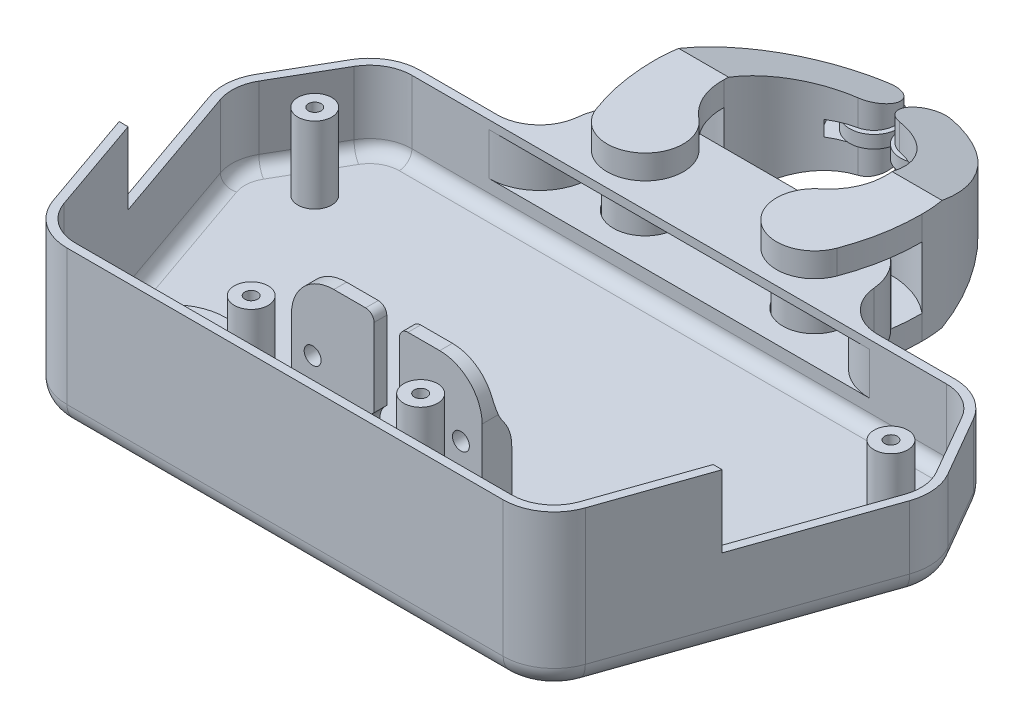
SolidWorks part; units mm, degrees
ref_plane "Front Plane" through (0, 0, 0) normal (0, 0, 1) x (1, 0, 0)
ref_plane "Top Plane" through (0, 0, 0) normal (0, 1, 0) x (1, 0, 0)
ref_plane "Right Plane" through (0, 0, 0) normal (1, 0, 0) x (0, 0, -1)
sketch "Sketch1" plane through (0, 0, 0) normal (0, 1, 0) x (1, 0, 0)
  line L0 (-70, -55) -> (-35, -55)
  line L1 (70, -55) -> (84.4338, -80)
  line L2 (84.4338, -80) -> (60, -150)
  line L3 (60, -150) -> (-60, -150)
  line L4 (-60, -150) -> (-84.4338, -80)
  line L5 (-84.4338, -80) -> (-70, -55)
  line L6 (-35, -55) -> (-35, -35)
  line L7 (-35, -35) -> (35, -35)
  line L8 (35, -35) -> (35, -55)
  line L9 (0, -55) -> (0, -122.8119) construction
  line L10 (35, -55) -> (70, -55)
  point P15 (0, -150)
  dimension "D1" = 25
  dimension "D2" = 140
  dimension "D3" = 70
  dimension "D4" = 120
  dimension "D5" = 70
  dimension "D6" = 55
  dimension "D7" = 120
  dimension "D8" = 20
  dimension "D9" = 70
  dimension "D10" = 35
extrude "Boss-Extrude1" add sketch "Sketch1" along normal blind 2
sketch "Sketch2" plane through (0, 2, 0) normal (0, 1, 0) x (1, 0, 0)
  line L0 (84.4338, -80) -> (70, -55) construction
  line L1 (60, -150) -> (84.4338, -80) construction
  line L2 (-60, -150) -> (60, -150) construction
  line L3 (-84.4338, -80) -> (-60, -150) construction
  line L4 (-70, -55) -> (-84.4338, -80) construction
  line L6 (84.4338, -80) -> (70, -55)
  line L7 (60, -150) -> (84.4338, -80)
  line L8 (-60, -150) -> (60, -150)
  line L9 (-84.4338, -80) -> (-60, -150)
  line L10 (-70, -55) -> (-84.4338, -80)
  line L11 (70, -55) -> (35, -55)
  line L12 (68.8453, -57) -> (33, -57)
  line L13 (-68.8453, -57) -> (-82.2434, -80.2062)
  line L14 (-82.2434, -80.2062) -> (-58.5798, -148)
  line L15 (-58.5798, -148) -> (58.5798, -148)
  line L16 (58.5798, -148) -> (82.2434, -80.2062)
  line L17 (82.2434, -80.2062) -> (68.8453, -57)
  line L18 (-35, -55) -> (-35, -35)
  line L19 (-35, -35) -> (35, -35)
  line L20 (35, -35) -> (35, -55)
  line L21 (-35, -55) -> (-70, -55)
  line L22 (-33, -57) -> (-33, -37)
  line L23 (70, -55) -> (-70, -55) construction
  line L24 (-33, -37) -> (33, -37)
  line L25 (33, -37) -> (33, -57)
  line L26 (-33, -57) -> (-68.8453, -57)
  line L28 (68.8453, -57) -> (-68.8453, -57) construction
  dimension "D1" = 2
  dimension "D2" = 2
  dimension "D3" = 2
  dimension "D4" = 2
extrude "Boss-Extrude2" add sketch "Sketch2" along normal blind 35
sketch "Sketch20" plane through (0, 0, 0) normal (0, -1, 0) x (1, 0, 0)
  line L0 (70, 55) -> (35, 55) construction
  line L1 (-35, 35) -> (35, 35)
  line L2 (-35, 35) -> (-35, 55)
  line L3 (-35, 55) -> (35, 55)
  line L4 (35, 35) -> (35, 55)
  line L5 (35, 55) -> (35, 35) construction
  line L6 (35, 35) -> (-35, 35) construction
  line L7 (-35, 35) -> (-35, 55) construction
extrude "Cut-Extrude7" cut sketch "Sketch20" against normal blind 8
sketch "Sketch21" plane through (0, 8, 0) normal (0, -1, 0) x (1, 0, 0)
  line L1 (-35, 35) -> (35, 35)
  line L2 (-35, 35) -> (-35, 55)
  line L3 (-35, 55) -> (35, 55)
  line L4 (35, 35) -> (35, 55)
extrude "Boss-Extrude12" add sketch "Sketch21" along normal blind 2
sketch "Sketch22" plane through (0, 0, 55) normal (0, 0, 1) x (1, 0, 0)
  line L1 (-33, 2) -> (33, 2)
  line L2 (-33, 2) -> (-33, 8)
  line L3 (-33, 8) -> (33, 8)
  line L4 (33, 2) -> (33, 8)
extrude "Boss-Extrude13" add sketch "Sketch22" along normal blind 2
sketch "Sketch23" plane through (0, 37, 0) normal (0, 1, 0) x (1, 0, 0)
  line L0 (35, -35) -> (-35, -35) construction
  line L1 (-35, -57) -> (35, -57)
  line L2 (-35, -57) -> (-35, -35)
  line L3 (-35, -35) -> (35, -35)
  line L4 (35, -57) -> (35, -35)
  line L5 (-35, -35) -> (-35, -55) construction
  line L6 (35, -55) -> (35, -35) construction
  line L7 (33, -57) -> (-33, -57) construction
extrude "Cut-Extrude8" cut sketch "Sketch23" against normal offset from surface (19 mm away) 12 up to face at (0, 6, 45)
sketch "Sketch24" plane through (0, 18, 0) normal (0, 1, 0) x (1, 0, 0)
  line L1 (-35, -35) -> (35, -35)
  line L2 (-35, -35) -> (-35, -57)
  line L3 (-35, -57) -> (35, -57)
  line L4 (35, -35) -> (35, -57)
  line L5 (-35, -35) -> (35, -35) construction
  line L6 (-35, -55) -> (-35, -35) construction
  line L8 (35, -35) -> (35, -55) construction
  line L9 (-35, -57) -> (-68.8453, -57) construction
extrude "Boss-Extrude16" add sketch "Sketch24" along normal blind 2
sketch "Sketch26" plane through (0, 0, 0) normal (0, -1, 0) x (1, 0, 0)
  line L0 (0, 35) -> (0, 168.1743) construction
  line L1 (-35, 35) -> (35, 35) construction
  circle A0 centre (20, 45) radius 7.5
  circle A1 centre (-20, 45) radius 7.5
  dimension "D1" = 15
  dimension "D2" = 10
  dimension "D3" = 20
extrude "Cut-Extrude9" cut sketch "Sketch26" against normal through all
sketch "Sketch27" plane through (0, 8, 0) normal (0, 1, 0) x (1, 0, 0)
  line L0 (-29.5, -45) -> (-27.5, -45)
  line L1 (-10.5, -45) -> (-12.5, -45)
  line L2 (0, -35) -> (0, -72.4721) construction
  line L3 (35, -35) -> (-35, -35) construction
  line L4 (29.5, -45) -> (27.5, -45)
  line L5 (10.5, -45) -> (12.5, -45)
  arc A0 (-27.5, -45) -> (-12.5, -45) centre (-20, -45) cw
  circle A1 centre (-20, -45) radius 7.5 construction
  arc A2 (-10.5, -45) -> (-29.5, -45) centre (-20, -45) ccw
  arc A3 (27.5, -45) -> (12.5, -45) centre (20, -45) ccw
  arc A4 (10.5, -45) -> (29.5, -45) centre (20, -45) cw
  dimension "D1" = 9.5
extrude "Boss-Extrude18" add sketch "Sketch27" along normal up to surface (10 mm away) up to face at (20, 18, 52.5)
sketch "Sketch25" plane through (0, 20, 0) normal (0, 1, 0) x (1, 0, 0)
  line L0 (35, -57) -> (35, -55) construction
  line L1 (-35, -57) -> (35, -57)
  line L2 (-35, -57) -> (-35, -55)
  line L3 (-35, -55) -> (35, -55)
  line L4 (35, -57) -> (35, -55)
  line L5 (-35, -57) -> (35, -57) construction
  line L6 (-35, -55) -> (-35, -57) construction
  line L7 (-35, -55) -> (-70, -55) construction
extrude "Boss-Extrude17" add sketch "Sketch25" along normal up to surface (17 mm away) up to face at (0, 37, 85.2758)
fillet "Fillet8" radius 10 2 edges at (-33, 13, 37) (33, 13, 37)
fillet "Fillet9" radius 12 2 edges at (35, 13, 35) (-35, 13, 35)
sketch "Sketch32" plane through (0, 6, 0) normal (0, -1, 0) x (1, 0, 0)
  circle A0 centre (-20, 45) radius 7.3
  circle A1 centre (-20, 45) radius 7.5 construction
  dimension "D1" = 14.6
extrude "Boss-Extrude22" add sketch "Sketch32" against normal offset from surface (14.6 mm away) 0.3 from offset 0.3 separate body up to face at (0, 20, 44.8382) offset beyond the face yes
ref_plane "Plane6" through (0, 13, 0) normal (0, -1, 0) x (-1, 0, 0)
sketch "Sketch34" plane through (0, 13, 0) normal (0, -1, 0) x (-1, 0, 0)
  line L0 (0, -55) -> (0, -6.1056) construction
  line L1 (-35, -55) -> (35, -55) construction
  circle A0 centre (6, -5) radius 6
  circle A1 centre (20, -45) radius 7.5 construction
  circle A2 centre (20, -45) radius 7.5 construction
  circle A3 centre (6, -5) radius 2.8
  dimension "D1" = 12
  dimension "D3" = 5.6
  dimension "D2" = 40
extrude "Boss-Extrude23" add sketch "Sketch34" along normal mid plane 3 separate body
sketch "Sketch36" plane through (0, 13, 0) normal (0, -1, 0) x (-1, 0, 0)
  circle A0 centre (6, -5) radius 2.5
  dimension "D1" = 5
extrude "Boss-Extrude24" add sketch "Sketch36" along normal mid plane 3.6 separate body
sketch "Sketch37" plane through (0, 11.2, 0) normal (0, -1, 0) x (1, 0, 0)
  line L0 (-1.0485, 27.7767) -> (-20, 45) construction
  line L1 (-6, 5) -> (-1.0485, 27.7767) construction
  line L2 (0.4994, 31.2114) -> (-20, 45) construction
  line L3 (0.4994, 31.2114) -> (-6, 5) construction
  arc A0 (-4.9378, 9.8859) -> (-7.2034, 0.147) centre (-6, 5) cw
  circle A1 centre (-20, 45) radius 7.3 construction
  arc A2 (-14.5977, 40.0903) -> (-26.0572, 49.0743) centre (-20, 45) ccw construction
  arc A3 (-4.9378, 9.8859) -> (-14.5977, 40.0903) centre (-1.0485, 27.7767) cw construction
  arc A4 (-26.0572, 49.0743) -> (-7.2034, 0.147) centre (0.4994, 31.2114) ccw construction
  arc A5 (-31.5058, 31.1575) -> (-19.3412, 27.0121) centre (-20, 45) ccw
  arc A6 (-31.5058, 31.1575) -> (-7.2034, 0.147) centre (0.4994, 31.2114) ccw
  arc A7 (-19.3412, 27.0121) -> (-4.9378, 9.8859) centre (-1.0485, 27.7767) ccw
  point P13 (0, 0)
  point P15 (0, 0)
  point P16 (-17.4466, 19.6336)
  point P17 (0, 0)
  dimension "D1" = 5
  dimension "D4" = 18
  dimension "D2" = 60
  dimension "D3" = 70
extrude "Boss-Extrude25" add sketch "Sketch37" along normal up to surface (11.2 mm away) up to face at (0, 0, 95)
sketch "Sketch39" plane through (0, 5.7, 0) normal (0, -1, 0) x (1, 0, 0)
  arc A0 (-14.3618, 37.985) -> (-28.4223, 48.1725) centre (-20, 45) ccw
  arc A1 (-31.5058, 31.1575) -> (-19.3412, 27.0121) centre (-20, 45) ccw construction
  arc A2 (-31.5058, 31.1575) -> (-19.3412, 27.0121) centre (-20, 45) ccw
  arc A3 (-31.5058, 31.1575) -> (-28.4223, 48.1725) centre (16.5339, 31.2385) cw
  arc A4 (-31.5058, 31.1575) -> (-7.2034, 0.147) centre (0.4994, 31.2114) ccw construction
  arc A5 (-19.3412, 27.0121) -> (-14.3618, 37.985) centre (-5.9908, 27.5701) cw
  arc A6 (-19.3412, 27.0121) -> (-4.9378, 9.8859) centre (-1.0485, 27.7767) ccw construction
  point P7 (-14.1628, 38.1497)
  point P8 (0, 0)
  dimension "D1" = 18
extrude "Boss-Extrude26" add sketch "Sketch39" along direction (0, -1, 0) on the side of the normal up to surface (5.7 mm away) up to face at (-16.6721, 0, 14.8228)
sketch "Sketch40" plane through (0, 20.3, 0) normal (0, 1, 0) x (1, 0, 0)
  arc A1 (-28.4223, -48.1725) -> (-14.3618, -37.985) centre (-20, -45) ccw construction
  arc A2 (-19.3412, -27.0121) -> (-14.3618, -37.985) centre (-5.9908, -27.5701) ccw construction
  arc A3 (-19.3412, -27.0121) -> (-31.5058, -31.1575) centre (-20, -45) ccw construction
  arc A4 (-31.5058, -31.1575) -> (-28.4223, -48.1725) centre (16.5339, -31.2385) ccw construction
  arc A5 (-28.4223, -48.1725) -> (-14.3618, -37.985) centre (-20, -45) ccw
  arc A6 (-19.3412, -27.0121) -> (-14.3618, -37.985) centre (-5.9908, -27.5701) ccw
  arc A7 (-19.3412, -27.0121) -> (-31.5058, -31.1575) centre (-20, -45) ccw
  arc A8 (-31.5058, -31.1575) -> (-28.4223, -48.1725) centre (16.5339, -31.2385) ccw
extrude "Boss-Extrude27" add sketch "Sketch40" along normal blind 5.7
sketch "Sketch41" plane through (0, 14.8, 0) normal (0, 1, 0) x (1, 0, 0)
  arc A0 (-4.9378, -9.8859) -> (-7.2034, -0.147) centre (-6, -5) ccw construction
  arc A1 (-19.3412, -27.0121) -> (-31.5058, -31.1575) centre (-20, -45) ccw construction
  arc A2 (-4.9378, -9.8859) -> (-19.3412, -27.0121) centre (-1.0485, -27.7767) ccw construction
  arc A3 (-7.2034, -0.147) -> (-31.5058, -31.1575) centre (0.4994, -31.2114) ccw construction
  arc A4 (-4.9378, -9.8859) -> (-7.2034, -0.147) centre (-6, -5) ccw
  arc A5 (-19.3412, -27.0121) -> (-31.5058, -31.1575) centre (-20, -45) ccw
  arc A6 (-4.9378, -9.8859) -> (-19.3412, -27.0121) centre (-1.0485, -27.7767) ccw
  arc A7 (-7.2034, -0.147) -> (-31.5058, -31.1575) centre (0.4994, -31.2114) ccw
extrude "Boss-Extrude28" add sketch "Sketch41" along normal up to surface (11.2 mm away) up to face at (-22.355, 26, 38.2867)
sketch "Sketch43" plane through (0, 11.2, 0) normal (0, 1, 0) x (1, 0, 0)
  arc A1 (-4.9378, -9.8859) -> (-19.3412, -27.0121) centre (-1.0485, -27.7767) ccw construction
  arc A3 (-19.3412, -27.0121) -> (-31.5058, -31.1575) centre (-20, -45) ccw construction
  arc A5 (-10.5927, -12.1524) -> (-19.3412, -27.0121) centre (-1.0485, -27.7767) ccw
  arc A6 (-7.2034, -0.147) -> (-31.5058, -31.1575) centre (0.4994, -31.2114) ccw construction
  arc A7 (-19.3412, -27.0121) -> (-31.5058, -31.1575) centre (-20, -45) ccw
  arc A8 (-14.2062, -2.7847) -> (-10.5927, -12.1524) centre (-6, -5) ccw
  arc A9 (-14.2062, -2.7847) -> (-31.5058, -31.1575) centre (0.4994, -31.2114) ccw
  arc A13 (-4.9378, -9.8859) -> (-7.2034, -0.147) centre (-6, -5) ccw construction
  point P1 (0, 0)
  point P7 (0, 0)
  point P11 (0, 0)
  point P14 (0, 0)
  point P17 (0, 0)
  point P18 (-28.8978, -29.353)
  dimension "D1" = 17
extrude "Boss-Extrude29" add sketch "Sketch43" along normal up to surface (3.6 mm away) up to face at (-6, 14.8, 2.5)
sketch "Sketch44" plane through (0, 0, 0) normal (1, 0, 0) x (0, 0, -1)
  line L0 (0, 17.8) -> (-26.0121, 26)
  line L1 (-26.0121, 26) -> (0, 26)
  line L4 (0, 14.8) -> (0, 26) construction
  line L5 (-9.8859, 26) -> (-27.0121, 26) construction
  line L6 (0, 17.8) -> (0, 26)
  line L7 (-15.422, 13) -> (22.0298, 13) construction
  line L8 (-47.6114, 13) -> (47.6114, 13) construction
  line L9 (0, 8.2) -> (-26.0121, 0)
  line L10 (-26.0121, 0) -> (0, 0)
  line L11 (0, 8.2) -> (0, 0)
  dimension "D1" = 1
  dimension "D2" = 3
extrude "Cut-Extrude10" cut sketch "Sketch44" against normal up to surface (31.0807 mm away) up to face at (-19.4078, 13, 12.2011)
ref_plane "Plane2" through (0, 0, 0) normal (1, 0, 0) x (0, 0, -1)
ref_plane "Plane3" through (0, 0, 126) normal (0, 0, -1) x (-1, 0, 0)
sketch "Sketch45" plane through (0, 13, 0) normal (0, -1, 0) x (-1, 0, 0)
  circle A0 centre (6, -5) radius 6 construction
  circle A1 centre (6, -5) radius 6
  circle A2 centre (6, -5) radius 5.75
  dimension "D1" = 11.5
extrude "Cut-Extrude11" cut sketch "Sketch45" along normal up to surface (1.5 mm away) from surface up to face at (-6, 11.5, -1) starting at face at (-6, 14.5, -1)
mirror "Mirror8" about plane through (0, 0, 0) normal (1, 0, 0) of bodies 137 140
sketch "Sketch8" plane through (0, 0, 126) normal (0, 0, -1) x (-1, 0, 0)
  line L0 (-68.8453, 2) -> (68.8453, 2) construction
  line L1 (-68.8453, 2) -> (68.8453, 2) construction
  line L2 (60, 0) -> (-60, 0) construction
  line L3 (22.5, 2) -> (-22.5, 2)
  line L4 (22.5, 2) -> (22.5, 36)
  line L5 (22.5, 36) -> (-22.5, 36)
  line L6 (-22.5, 2) -> (-22.5, 36)
  line L7 (60, 0) -> (-60, 0) construction
  line L8 (0, 14.8493) -> (0, -14.8493) construction
  dimension "D1" = 34
  dimension "D2" = 45
  dimension "D3" = 22.5
extrude "Boss-Extrude5" add sketch "Sketch8" along normal blind 3
sketch "Sketch9" plane through (0, 2, 0) normal (0, 1, 0) x (1, 0, 0)
  line L1 (-22.5, -123) -> (-19.5, -123)
  line L2 (-22.5, -123) -> (-22.5, -119)
  line L3 (-22.5, -119) -> (-19.5, -119)
  line L4 (-19.5, -123) -> (-19.5, -119)
  line L5 (22.5, -123) -> (19.5, -123)
  line L6 (22.5, -123) -> (22.5, -119)
  line L7 (22.5, -119) -> (19.5, -119)
  line L8 (19.5, -123) -> (19.5, -119)
  dimension "D1" = 3
  dimension "D2" = 4
extrude "Boss-Extrude6" add sketch "Sketch9" along normal blind 20
fillet "Fillet1" radius 10 2 edges at (-21, 22, 123) (21, 22, 123)
fillet "Fillet2" radius 10 2 edges at (-21, 22, 119) (21, 22, 119)
sketch "Sketch11" plane through (0, 2, 0) normal (0, 1, 0) x (1, 0, 0)
  line L0 (-58.5798, -148) -> (58.5798, -148) construction
  circle A0 centre (-43.5798, -133) radius 12.5
  dimension "D1" = 25
  dimension "D2" = 15
  dimension "D3" = 15
extrude "Boss-Extrude9" add sketch "Sketch11" along normal blind 10
ref_plane "Plane4" through (0, 7, 0) normal (0, 1, 0) x (1, 0, 0)
sketch "Sketch13" plane through (0, 7, 0) normal (0, 1, 0) x (1, 0, 0)
  line L0 (-53.0211, -136.2955) -> (-58.294, -121.1894)
  line L1 (-82.2434, -80.2062) -> (-58.5798, -148) construction
  line L2 (-34.1384, -129.7045) -> (-39.4113, -114.5983)
  line L3 (-58.294, -121.1894) -> (-39.4113, -114.5983)
  arc A0 (-53.0211, -136.2955) -> (-34.1384, -129.7045) centre (-43.5798, -133) ccw
  dimension "D1" = 20
  dimension "D2" = 16
extrude "Cut-Extrude3" cut sketch "Sketch13" along normal blind 5 from offset 3 offset against normal yes
sketch "Sketch14" plane through (0, 12, 0) normal (0, 1, 0) x (1, 0, 0)
  circle A0 centre (-43.5798, -133) radius 2.5
  circle A1 centre (-43.5798, -133) radius 12.5 construction
  dimension "D1" = 5
extrude "Cut-Extrude4" cut sketch "Sketch14" against normal up to surface (8 mm away) up to face at (-44.4037, 4, 130.6397)
sketch "Sketch15" plane through (0, 0, 126) normal (0, 0, 1) x (1, 0, 0)
  line L1 (22.5, 2) -> (-22.5, 2) construction
  line L2 (22.5, 2) -> (-22.5, 2) construction
  line L3 (0, -14.8493) -> (0, 14.8493) construction
  circle A0 centre (17.5, 20) radius 2
  circle A1 centre (-17.5, 20) radius 2
  circle A3 centre (0, 12) radius 4.65
  dimension "D1" = 8
  dimension "D2" = 4
  dimension "D3" = 4
  dimension "D6" = 9.3
  dimension "D4" = 35
  dimension "D5" = 17.5
  dimension "D7" = 10
extrude "Cut-Extrude5" cut sketch "Sketch15" against normal up to surface (3 mm away) up to face at (0, 24.5, 123)
fillet "Fillet3" radius 10 8 edges at (-35, 13, 55) (35, 13, 55) (58.5798, 19.5, 148) (-58.5798, 19.5, 148) (82.2434, 19.5, 80.2062) (68.8453, 19.5, 57) (-82.2434, 19.5, 80.2062) (-68.8453, 19.5, 57)
fillet "Fillet4" radius 12 8 edges at (-60, 18.5, 150) (-84.4338, 18.5, 80) (-70, 18.5, 55) (-33, 13, 57) (33, 13, 57) (70, 18.5, 55) (60, 18.5, 150) (84.4338, 18.5, 80)
fillet "Fillet5" radius 10 2 edges at (22.5, 36, 124.5) (-22.5, 36, 124.5)
fillet "Fillet6" radius 3 12 edges at (-70.8266, 2, 112.9143) (-81.2478, 2, 80.3) (-75.842, 2, 69.1187) (-68.0718, 2, 58.3397) (0, 2, 57) (68.0718, 2, 58.3397) (75.842, 2, 69.1187) (81.2478, 2, 80.3) (70.8266, 2, 112.9143) (0, 2, 148) (-57.2685, 2, 146.1534) (57.2685, 2, 146.1534)
fillet "Fillet7" radius 5 12 edges at (69.0718, 0, 56.6077) (77.5741, 0, 68.1187) (83.2389, 0, 80.1125) (72.7148, 0, 113.5734) (58.4264, 0, 147.7841) (0, 0, 150) (-58.4264, 0, 147.7841) (-72.7148, 0, 113.5734) (-83.2389, 0, 80.1125) (-77.5741, 0, 68.1187) (-69.0718, 0, 56.6077) (0, 0, 55)
sketch "Sketch16" plane through (0, 0, 0) normal (1, 0, 0) x (0, 0, -1)
  line L0 (-83.5443, 0) -> (-140.3069, 0) construction
  line L1 (-118, 40) -> (-28, 40)
  line L2 (-118, 40) -> (-118, 20)
  line L3 (-118, 20) -> (-28, 20)
  line L4 (-28, 40) -> (-28, 20)
  line L5 (-150, 5) -> (-150, 37) construction
  dimension "D1" = 20
  dimension "D2" = 32
  dimension "D3" = 20
  dimension "D4" = 90
extrude "Cut-Extrude6" cut sketch "Sketch16" against normal through all both and the other way through all
sketch "Sketch17" plane through (0, 2, 0) normal (0, 1, 0) x (1, 0, 0)
  line L0 (0, -14.8493) -> (0, 14.8493) construction
  line L4 (-63.0718, -55) -> (-44.9089, -55) construction
  circle A2 centre (-68, -75) radius 4
  circle A4 centre (-68, -75) radius 1.5
  circle A10 centre (68, -75) radius 1.5
  circle A11 centre (68, -75) radius 4
  dimension "D7" = 8
  dimension "D9" = 3
  dimension "D4" = 20
  dimension "D5" = 68
extrude "Boss-Extrude10" add sketch "Sketch17" along normal up to surface (18 mm away) up to face at (0, 20, 71.1525)
sketch "Sketch19" plane through (0, 2, 0) normal (0, 1, 0) x (1, 0, 0)
  line L0 (0, -14.8493) -> (0, 14.8493) construction
  line L1 (-51.4786, -150) -> (51.4786, -150) construction
  circle A0 centre (-20, -138) radius 4
  circle A1 centre (-20, -138) radius 1.5
  circle A2 centre (20, -138) radius 1.5
  circle A3 centre (20, -138) radius 4
  dimension "D1" = 3
  dimension "D2" = 8
  dimension "D3" = 20
  dimension "D4" = 12
extrude "Boss-Extrude11" add sketch "Sketch19" along normal up to surface (35 mm away) up to face at (0, 37, 136.7604)
sketch "Sketch46" plane through (0, 0, 126) normal (0, 0, 1) x (1, 0, 0)
  line L0 (-3, 12) -> (-3, 36)
  line L1 (-3, 36) -> (3, 36)
  line L3 (-3, 12) -> (3, 12)
  line L5 (-12.5, 36) -> (12.5, 36) construction
  line L7 (3, 36) -> (3, 12)
  circle A0 centre (0, 12) radius 4.65 construction
  circle A1 centre (0, 12) radius 4.65 construction
  point P6 (0, 0)
  dimension "D1" = 6
extrude "Cut-Extrude12" cut sketch "Sketch46" against normal up to surface (3 mm away) up to face at (-4.65, 12, 123)
fillet "Fillet10" radius 2 2 edges at (-3, 36, 124.5) (3, 36, 124.5)
